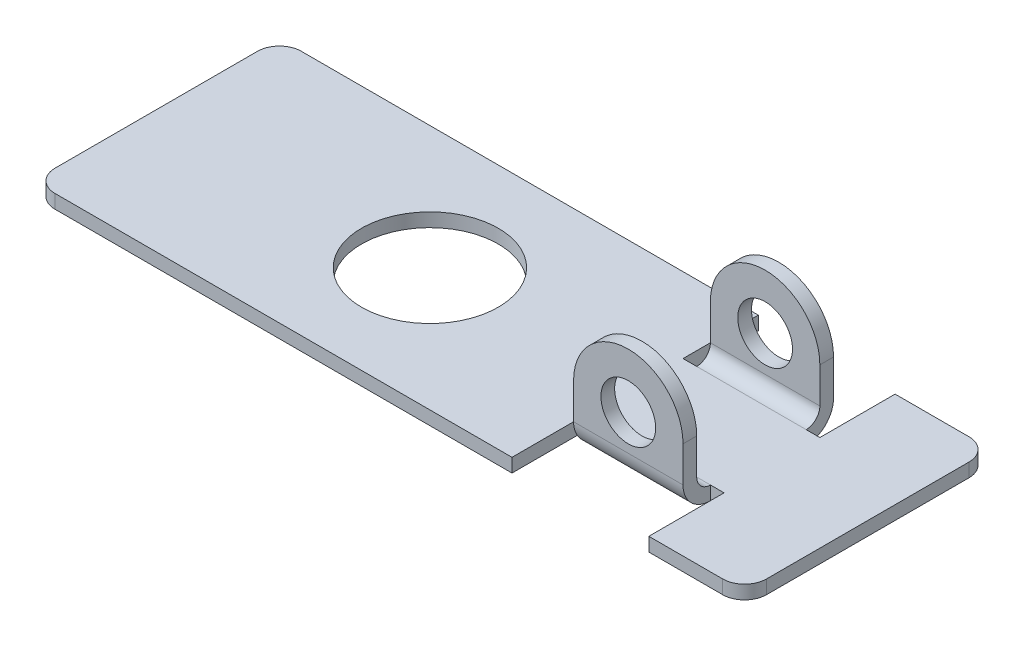
SolidWorks part; units mm, degrees
ref_plane "Спереди" through (0, 0, 0) normal (0, 0, 1) x (1, 0, 0)
ref_plane "Сверху" through (0, 0, 0) normal (0, 1, 0) x (1, 0, 0)
ref_plane "Справа" through (0, 0, 0) normal (1, 0, 0) x (0, 0, -1)
sketch "Эскиз1" plane through (0, 0, 0) normal (0, 1, 0) x (1, 0, 0)
  line L0 (10, 2.75) -> (10, -2.75) construction
  line L1 (-10, 4.5) -> (7.5, 4.5)
  line L2 (-10, 4.5) -> (-10, -4.5)
  line L3 (-10, -4.5) -> (7.5, -4.5)
  line L4 (16, 4.5) -> (16, -4.5)
  line L7 (7.5, 4.5) -> (7.5, 1.75)
  line L8 (12.5, 4.5) -> (16, 4.5)
  line L10 (8, 2.75) -> (12, 2.75)
  line L11 (12.5, 1.75) -> (12.5, 4.5)
  line L12 (12.5, -4.5) -> (12.5, -1.75)
  line L13 (12, -2.75) -> (8, -2.75)
  line L14 (7.5, -1.75) -> (7.5, -4.5)
  line L16 (12.5, -4.5) -> (16, -4.5)
  line L18 (7.5, 1.75) -> (8, 1.75)
  line L19 (8, 2.75) -> (8, 1.75)
  line L22 (12.5, 1.75) -> (12, 1.75)
  line L23 (12, 2.75) -> (12, 1.75)
  line L26 (12.5, -1.75) -> (12, -1.75)
  line L27 (12, -2.75) -> (12, -1.75)
  line L30 (7.5, -1.75) -> (8, -1.75)
  line L31 (8, -2.75) -> (8, -1.75)
  circle A0 centre (0, 0) radius 2.5
  point P12 (-10, 0)
  point P14 (10, -2.75)
  point P34 (10, 0)
  dimension "D3" = 5
  dimension "D1" = 9
  dimension "D2" = 10
  dimension "D4" = 1
  dimension "D5" = 0.5
  dimension "D6" = 5.5
  dimension "D7" = 10
  dimension "D8" = 6
  dimension "D9" = 4
extrude "Бобышка-Вытянуть1" add sketch "Эскиз1" along normal blind 0.5
ref_plane "Плоскость1" through (0, 0, 0) normal (0, 0, 1) x (1, 0, 0)
sketch "Эскиз2" plane through (0, 0, 0) normal (0, 0, 1) x (1, 0, 0)
  line L0 (8, 0.5) -> (8, 2.3)
  line L1 (-10, 0.5) -> (7.5, 0.5) construction
  line L2 (12, 2.3) -> (12, 0.5)
  line L3 (12, 0.5) -> (8, 0.5)
  line L6 (8, 0.5) -> (12, 0.5) construction
  arc A0 (8, 2.3) -> (12, 2.3) centre (10, 2.3) cw
  circle A1 centre (10, 2.3) radius 1
  point P12 (10, 0.5)
  point P13 (10, 0.5)
  dimension "D1" = 2
  dimension "D2" = 4
  dimension "D3" = 1.8
extrude "Бобышка-Вытянуть2" add sketch "Эскиз2" against normal blind 0.5 from surface starting at face at (10, 0.25, 2.75)
extrude "Бобышка-Вытянуть3" add sketch "Эскиз2<2>" along normal blind 0.5 from surface starting at face at (10, 0.25, -2.75)
sketch "Эскиз2<2>" plane through (0, 0, 0) normal (0, 0, 1) x (1, 0, 0) same geometry as "Эскиз2"
fillet "Скругление1" radius 0.8 4 edges at (-10, 0.25, -4.5) (-10, 0.25, 4.5) (16, 0.25, -4.5) (16, 0.25, 4.5)
fillet "Скругление2" radius 0.5 2 edges at (10, 0.5, 2.25) (10, 0.5, -2.25)
fillet "Скругление4" radius 1 2 edges at (10, 0, 2.75) (10, 0, -2.75)
